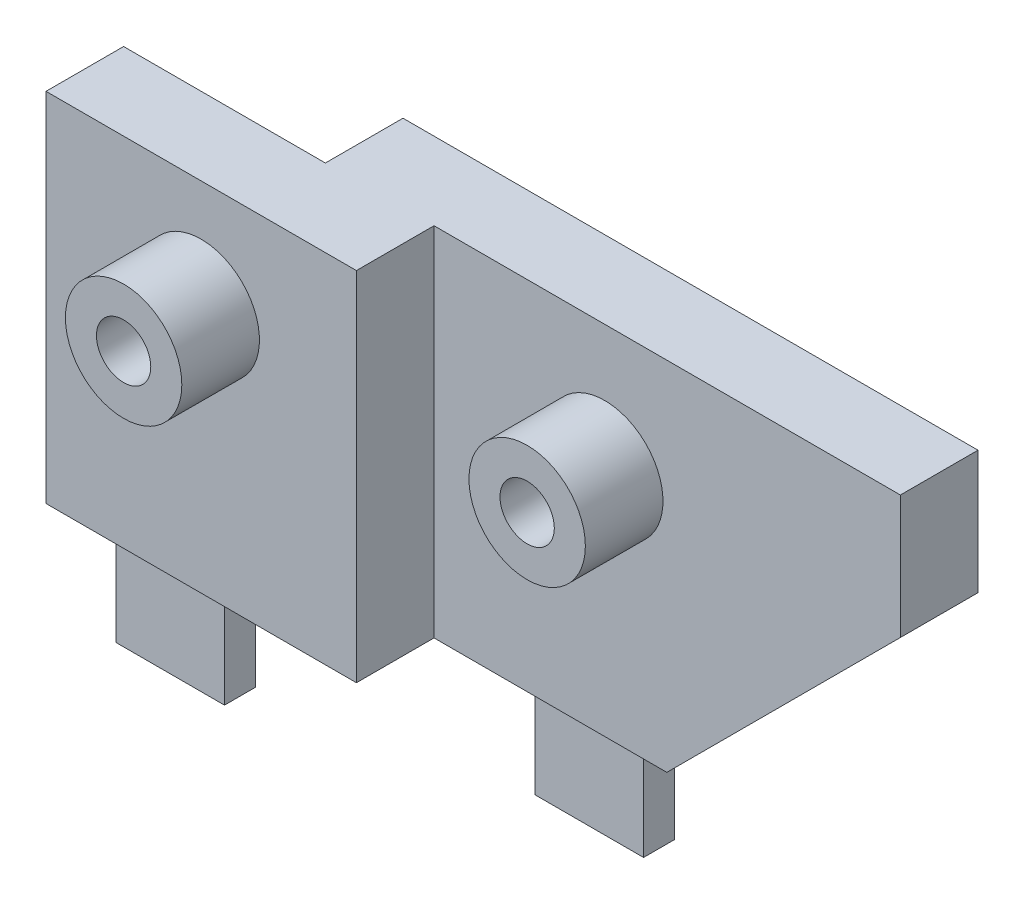
SolidWorks part; units mm, degrees
ref_plane "Front Plane" through (0, 0, 0) normal (0, 0, 1) x (1, 0, 0)
ref_plane "Top Plane" through (0, 0, 0) normal (0, 1, 0) x (1, 0, 0)
ref_plane "Right Plane" through (0, 0, 0) normal (1, 0, 0) x (0, 0, -1)
sketch "Sketch1" plane through (0, 0, 0) normal (0, 1, 0) x (1, 0, 0)
  line L10 (-18, -5.5617) -> (-18, -10) construction
  line L11 (0, 0) -> (-18, 0)
  line L12 (0, 0) -> (0, -5)
  line L13 (0, -5) -> (-15, -5)
  line L14 (-18, 0) -> (-18, -5.5617) construction
  line L15 (-22, -5) -> (-35, -5)
  line L16 (-15, -5) -> (-15, -10)
  line L17 (-15, -10) -> (-35, -10)
  line L18 (-35, -5) -> (-35, -10)
  line L19 (-18, 0) -> (-22, 0)
  line L20 (-22, 0) -> (-22, -5)
  dimension "D1" = 20
  dimension "D2" = 5
  dimension "D3" = 5
  dimension "D4" = 18
  dimension "D5" = 5
  dimension "D6" = 7
  dimension "D7" = 15
extrude "Boss-Extrude1" add sketch "Sketch1" along normal blind 23
sketch "Sketch2" plane through (0, 0, 10) normal (0, 0, 1) x (1, 0, 0)
  line L0 (-35, 23) -> (-35, 0) construction
  line L1 (-35, 0) -> (-15, 0) construction
  line L2 (-15, 0) -> (0, 0) construction
  line L3 (0, 23) -> (0, 0) construction
  circle A0 centre (-25, 16) radius 1.75
  circle A1 centre (-4, 15) radius 1.75
  dimension "D5" = 3.5
  dimension "D6" = 3.5
  dimension "D1" = 10
  dimension "D2" = 16
  dimension "D3" = 15
  dimension "D4" = 4
extrude "Cut-Extrude1" cut sketch "Sketch2" against normal through all
sketch "Sketch3" plane through (0, 0, 0) normal (0, -1, 0) x (1, 0, 0)
  line L0 (-22, 5) -> (-15, 5) construction
  line L1 (-18.5, 5) -> (-18.5, 10) construction
  line L2 (-35, 10) -> (-15, 10) construction
  line L3 (-18.5, 5) -> (-18.5, 0) construction
  line L4 (0, 0) -> (-22, 0) construction
  circle A0 centre (-18.5, 5) radius 1.5
  dimension "D1" = 3
extrude "Cut-Extrude2" cut sketch "Sketch3" against normal blind 10
sketch "Sketch4" plane through (0, 0, 0) normal (0, -1, 0) x (1, 0, 0)
  line L0 (-22, 2.5) -> (0, 2.5) construction
  line L1 (-22, 0) -> (-22, 5) construction
  line L2 (0, 5) -> (0, 0) construction
  line L3 (-15, 7.5) -> (-35, 7.5) construction
  line L4 (-15, 10) -> (-15, 5) construction
  line L5 (-35, 5) -> (-35, 10) construction
  line L7 (-10, 1.5) -> (-3, 1.5)
  line L8 (-10, 1.5) -> (-10, 3.5)
  line L9 (-10, 3.5) -> (-3, 3.5)
  line L10 (-3, 1.5) -> (-3, 3.5)
  line L11 (-10, 1.5) -> (-3, 3.5) construction
  line L12 (-10, 3.5) -> (-3, 1.5) construction
  line L13 (-32, 6.5) -> (-25, 6.5)
  line L14 (-32, 6.5) -> (-32, 8.5)
  line L15 (-32, 8.5) -> (-25, 8.5)
  line L16 (-25, 6.5) -> (-25, 8.5)
  line L17 (-32, 6.5) -> (-25, 8.5) construction
  line L18 (-32, 8.5) -> (-25, 6.5) construction
  point P12 (-6.5, 2.5)
  point P17 (-28.5, 7.5)
  dimension "D1" = 7
  dimension "D2" = 2
  dimension "D3" = 3
  dimension "D4" = 7
  dimension "D5" = 2
  dimension "D6" = 3
extrude "Boss-Extrude2" add sketch "Sketch4" along normal blind 7
sketch "Sketch5" plane through (0, 0, 10) normal (0, 0, 1) x (1, 0, 0)
  circle A0 centre (-25, 16) radius 1.75
  circle A1 centre (-25, 16) radius 3.75
  circle A2 centre (-25, 16) radius 1.75 construction
  dimension "D1" = 2
extrude "Boss-Extrude3" add sketch "Sketch5" along normal blind 5
sketch "Sketch6" plane through (0, 0, 5) normal (0, 0, 1) x (1, 0, 0)
  circle A0 centre (-4, 15) radius 1.75
  circle A1 centre (-4, 15) radius 1.75 construction
  circle A2 centre (-4, 15) radius 3.75
  dimension "D1" = 2
extrude "Boss-Extrude4" add sketch "Sketch6" along normal blind 5
sketch "Sketch7" plane through (0, 0, 5) normal (0, 0, 1) x (1, 0, 0)
  line L0 (0, 0) -> (0, 23)
  line L1 (0, 23) -> (15.0472, 23)
  line L2 (15.0472, 15.0472) -> (0, 0)
  line L3 (15.0472, 23) -> (15.0472, 15.0472)
  dimension "D1" = 45
  dimension "D2" = 21.28
extrude "Boss-Extrude5" add sketch "Sketch7" against normal blind 5
